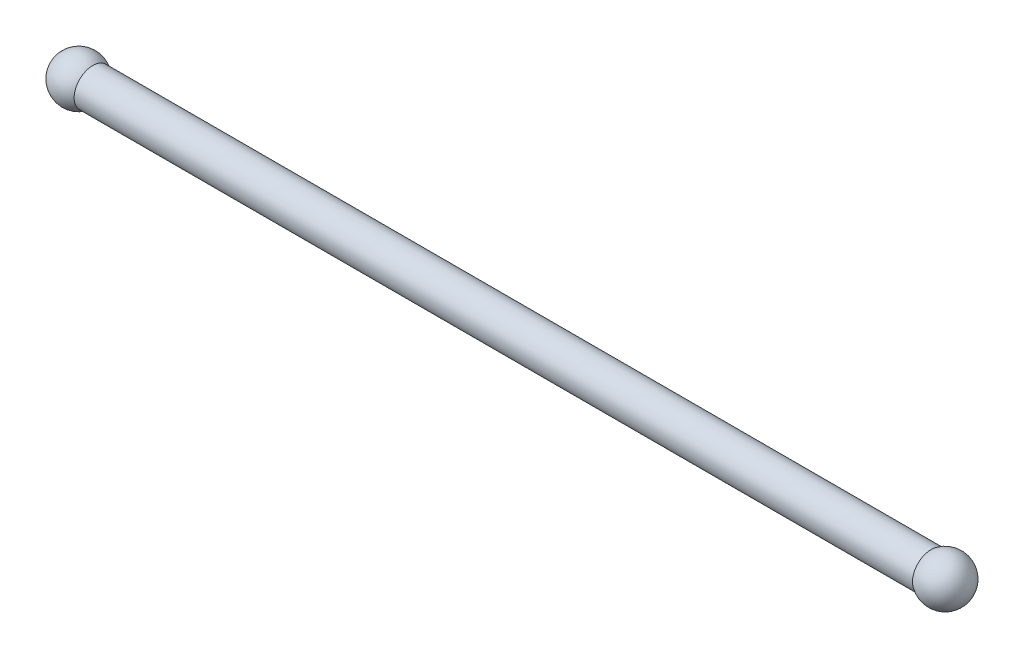
SolidWorks part; units mm, degrees
ref_plane "Front Plane" through (0, 0, 0) normal (0, 0, 1) x (1, 0, 0)
ref_plane "Top Plane" through (0, 0, 0) normal (0, 1, 0) x (1, 0, 0)
ref_plane "Right Plane" through (0, 0, 0) normal (1, 0, 0) x (0, 0, -1)
sketch "Sketch1" plane through (0, 0, 0) normal (1, 0, 0) x (0, 0, -1)
  circle A0 centre (0, 0) radius 1
  dimension "D1" = 2
extrude "Boss-Extrude1" add sketch "Sketch1" along normal blind 45
ref_plane "Plane1" through (22.5, 0, 0) normal (1, 0, 0) x (0, 0, -1)
dome "Dome1" faces to dome 1 distance 2 reverse direction no elliptical dome no face at (0, 0, -1) parameters "D1"=2
dome "Dome2" faces to dome 1 distance 2 reverse direction no elliptical dome no face at (45, 0, -1) parameters "D1"=2
